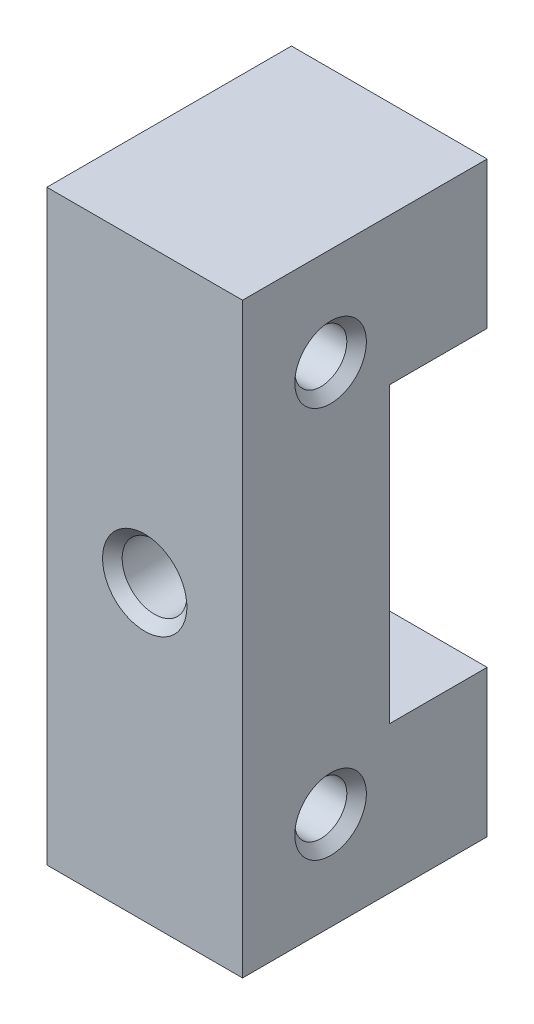
SolidWorks part; units mm, degrees
material "6061 Alloy"
ref_plane "Front Plane" through (0, 0, 0) normal (0, 0, 1) x (1, 0, 0)
ref_plane "Top Plane" through (0, 0, 0) normal (0, 1, 0) x (1, 0, 0)
ref_plane "Right Plane" through (0, 0, 0) normal (1, 0, 0) x (0, 0, -1)
sketch "Sketch1" plane through (0, 0, 0) normal (1, 0, 0) x (0, 0, -1)
  line L0 (-44.45, 241.3) -> (-12.7, 241.3) construction
  line L1 (-12.7, 241.3) -> (-12.7, 260.35) construction
  line L2 (-12.7, 260.35) -> (-25.4, 260.35) construction
  line L3 (-25.4, 260.35) -> (-25.4, 298.45) construction
  line L4 (-12.7, 298.45) -> (-12.7, 317.5) construction
  line L5 (-25.4, 298.45) -> (-12.7, 298.45) construction
  line L6 (-44.45, 317.5) -> (-44.45, 241.3) construction
  line L7 (-12.7, 317.5) -> (-44.45, 317.5) construction
  line L8 (-44.45, 241.3) -> (-12.7, 241.3)
  line L9 (-12.7, 241.3) -> (-12.7, 260.35)
  line L10 (-12.7, 260.35) -> (-25.4, 260.35)
  line L11 (-25.4, 260.35) -> (-25.4, 298.45)
  line L12 (-12.7, 298.45) -> (-12.7, 317.5)
  line L13 (-25.4, 298.45) -> (-12.7, 298.45)
  line L14 (-44.45, 317.5) -> (-44.45, 241.3)
  line L15 (-12.7, 317.5) -> (-44.45, 317.5)
  line L16 (-12.7, 298.45) -> (-12.7, 260.35) construction
  line L17 (-12.7, 279.4) -> (-25.4, 279.4) construction
  line L18 (-25.4, 279.4) -> (-44.45, 279.4) construction
  line L19 (-33.02, 304.8) -> (-33.02, 254) construction
  point P13 (-33.02, 279.4)
  dimension "D1" = 50.8
  dimension "D2" = 7.62
extrude "Boss-Extrude1" add sketch "Sketch1" along normal mid plane 25.4
sketch "Sketch4" plane through (12.7, 0, 0) normal (1, 0, 0) x (0, 0, -1)
  point P0 (-33.02, 304.8)
  point P3 (-33.02, 254)
hole_wizard "1/4 Clearance Hole1" positions "Sketch4" profile "Sketch3" hole size "1/4" standard "ANSI Inch" end condition through all
sketch "Sketch3" plane through (12.7, 304.8, 33.02) normal (0, 1, 0) x (0, 0, -1)
  line L0 (0, 0) -> (0, 25.4)
  line L1 (0, 25.4) -> (3.3782, 25.4)
  line L2 (3.3782, 25.4) -> (3.3782, 0)
  line L5 (3.3782, 0) -> (0, 0)
  line L11 (0, -6.35) -> (0, 107.95) construction
  dimension "Thru Hole Dia." = 6.7564
  dimension "Thru Hole Depth" = 25.4
sketch "Sketch7" plane through (0, 0, 25.4) normal (0, 0, -1) x (-1, 0, 0)
  line L0 (0, 317.5) -> (0, 241.3) construction
  point P0 (0, 279.4)
  point P7 (0, 279.4)
hole_wizard "M8 Clearance Hole1" positions "Sketch7" profile "Sketch6" hole size "M8" standard "ANSI Metric" end condition through all
sketch "Sketch6" plane through (0, 279.4, 25.4) normal (1, 0, 0) x (0, 1, 0)
  line L0 (0, 0) -> (0, 19.05)
  line L1 (0, 19.05) -> (4.2, 19.05)
  line L2 (4.2, 19.05) -> (4.2, 0)
  line L5 (4.2, 0) -> (0, 0)
  line L11 (0, -6.35) -> (0, 107.95) construction
  dimension "Thru Hole Dia." = 8.4
  dimension "Thru Hole Depth" = 19.05
chamfer "Chamfer1" distance 1.27 angle 45 6 edges at (-4.2, 279.4, 25.4) (-4.2, 279.4, 44.45) (12.7, 254, 29.6418) (-12.7, 254, 29.6418) (12.7, 304.8, 29.6418) (-12.7, 304.8, 29.6418)
